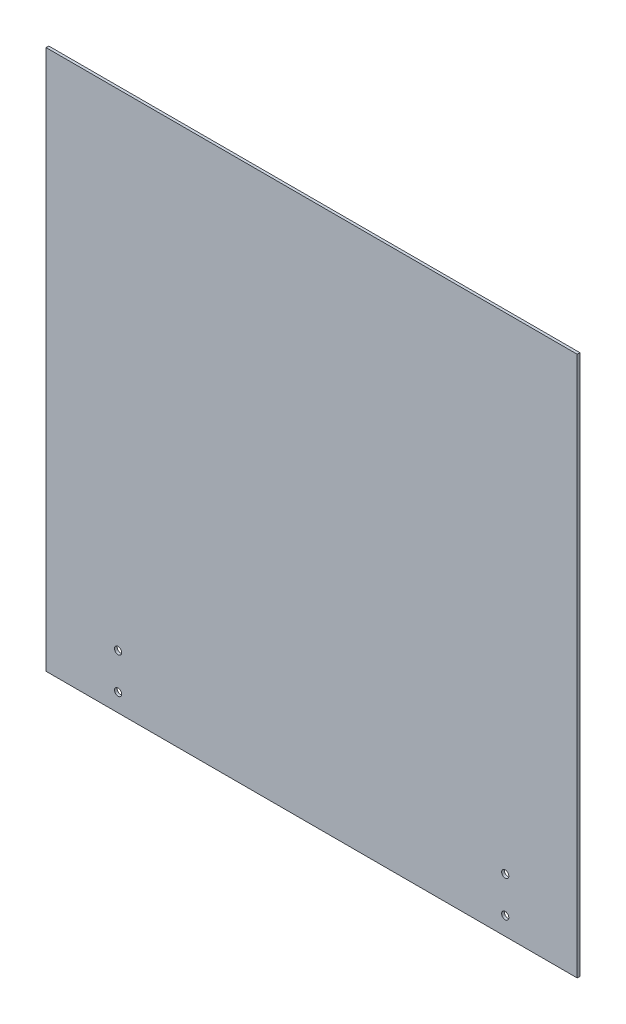
SolidWorks part; units mm, degrees
ref_plane "前视基准面" through (0, 0, 0) normal (0, 0, 1) x (1, 0, 0)
ref_plane "上视基准面" through (0, 0, 0) normal (0, 1, 0) x (1, 0, 0)
ref_plane "右视基准面" through (0, 0, 0) normal (1, 0, 0) x (0, 0, -1)
sketch "草图1" plane through (0, 0, 0) normal (0, 0, 1) x (1, 0, 0)
  line L1 (-147.5, -150) -> (147.5, -150)
  line L2 (-147.5, -150) -> (-147.5, 150)
  line L3 (-147.5, 150) -> (147.5, 150)
  line L4 (147.5, -150) -> (147.5, 150)
  line L5 (-147.5, -150) -> (147.5, 150) construction
  line L6 (-147.5, 150) -> (147.5, -150) construction
  circle A0 centre (107.5, -140) radius 2
  circle A1 centre (107.5, -120) radius 2
  circle A2 centre (-107.5, -120) radius 2
  circle A3 centre (-107.5, -140) radius 2
  point P0 (0, 0)
  dimension "D3" = 4
  dimension "D4" = 4
  dimension "D5" = 4
  dimension "D6" = 4
  dimension "D1" = 295
  dimension "D2" = 300
  dimension "D7" = 20
  dimension "D8" = 30
  dimension "D9" = 10
  dimension "D10" = 20
  dimension "D11" = 215
  dimension "D12" = 40
base flange "基体-法兰1" sketch "草图1" thickness 1.5 reverse thickness direction no parameters "D1"=0.7366
sketch "折弯-线1" plane through (0, 0, 0) normal (0, 1, 0) x (1, 0, 0)
sketch "边界框1" plane through (0, 0, 0) normal (0, 1, 0) x (1, 0, 0)
sheet metal parameters "钣金6" thickness 1.5 parameters "D1"=0.7366
flat pattern "平板型式6" [suppressed]
sketch "折弯-线2" plane through (0, 0, 0) normal (0, 1, 0) x (1, 0, 0)
sketch "边界框2" [suppressed] plane through (0, 0, 0) normal (0, 1, 0) x (1, 0, 0)
